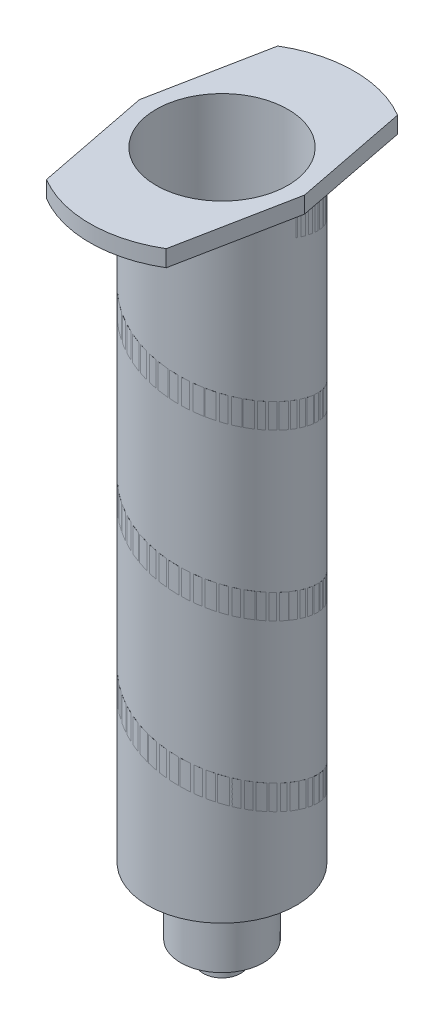
SolidWorks part; units mm, degrees
material "ABS PC"
ref_plane "Front Plane" through (0, 0, 0) normal (0, 0, 1) x (1, 0, 0)
ref_plane "Top Plane" through (0, 0, 0) normal (0, 1, 0) x (1, 0, 0)
ref_plane "Right Plane" through (0, 0, 0) normal (1, 0, 0) x (0, 0, -1)
sketch "Sketch2" plane through (0, 0, 0) normal (0, 1, 0) x (1, 0, 0)
  circle A0 centre (0, 0) radius 8.98
  circle A1 centre (0, 0) radius 7.98
  dimension "D1" = 17.96
  dimension "D2" = 1
extrude "Boss-Extrude1" add sketch "Sketch2" along normal blind 73
sketch "Sketch3" plane through (0, 73, 0) normal (0, 1, 0) x (1, 0, 0)
  line L0 (-10, 0) -> (10, 0) construction
  line L1 (10, -16) -> (-10, -16) construction
  line L2 (10, -16) -> (10, 16) construction
  line L3 (10, 16) -> (-10, 16) construction
  line L4 (-10, -16) -> (-10, 16) construction
  line L5 (10, -16) -> (-10, 16) construction
  line L6 (10, 16) -> (-10, -16) construction
  line L7 (7.25, -14) -> (-7.25, -14) construction
  line L8 (7.25, -14) -> (7.25, 14) construction
  line L9 (7.25, 14) -> (-7.25, 14) construction
  line L10 (-7.25, -14) -> (-7.25, 14) construction
  line L11 (7.25, -14) -> (-7.25, 14) construction
  line L12 (7.25, 14) -> (-7.25, -14) construction
  line L13 (-10, 0) -> (-7.25, -14)
  line L14 (7.25, -14) -> (10, 0)
  line L15 (10, 0) -> (7.25, 14)
  line L16 (-7.25, 14) -> (-10, 0)
  circle A0 centre (0, 0) radius 8.98
  arc A1 (-7.25, 14) -> (7.25, 14) centre (0, 1.8594) cw
  arc A2 (-7.25, -14) -> (7.25, -14) centre (0, -1.8594) ccw
  circle M1 centre (0, 0) radius 8.98
  circle M2 centre (0, 0) radius 7.98
  dimension "D1" = 32
  dimension "D2" = 20
  dimension "D3" = 14.5
  dimension "D4" = 28
extrude "Boss-Extrude2" add sketch "Sketch3" along normal blind 2 contours M1 M2 | M2 | L13 A2 L14 L15 A1 L16 M1 region at (-8.2547, 73, -6.9273) region at (-8.726, 73, 0) region at (0, 73, 0)
sketch "Sketch4" plane through (0, 0, 0) normal (1, 0, 0) x (0, 0, -1)
  line L0 (-8.98, 0) -> (8.98, 0)
  line L1 (8.98, 0) -> (8.98, 8.9522) construction
  line L2 (8.98, 0) -> (8.98, 73) construction
  line L3 (8.98, 8.9522) -> (-8.98, 8.9522) construction
  line L4 (-8.98, 73) -> (-8.98, 0) construction
  line L5 (-8.98, 8.9522) -> (-8.98, 0) construction
  line L6 (8.98, 0) -> (8.98, -1) construction
  line L7 (8.98, 0) -> (5, -1)
  line L8 (5, -2.9015) -> (-5, -2.9015) construction
  line L9 (5, -2.9015) -> (5, 2.9015) construction
  line L10 (5, 2.9015) -> (-5, 2.9015) construction
  line L11 (-5, -2.9015) -> (-5, 2.9015) construction
  line L12 (5, -2.9015) -> (-5, 2.9015) construction
  line L13 (5, 2.9015) -> (-5, -2.9015) construction
  line L14 (5, -1) -> (5, 0)
  line L15 (5, 0) -> (8.98, 0)
  line L16 (0, 0) -> (0, -7.0679) construction
  point P10 (0, 0)
  dimension "D1" = 1
  dimension "D2" = 10
revolve "Revolve1" add sketch "Sketch4" angle 360 about L16 region at (0, -0.3333, -6.3267)
ref_plane "Plane1" through (0, -1, 0) normal (0, -1, 0) x (-1, 0, 0)
sketch "Sketch6" plane through (0, -1, 0) normal (0, -1, 0) x (-1, 0, 0)
  circle A0 centre (0, 0) radius 5
  circle A1 centre (0, 0) radius 2.25
  dimension "D1" = 4.5
extrude "Boss-Extrude3" add sketch "Sketch6" along normal blind 0.5 separate body
sketch "Sketch7" plane through (0, -1, 0) normal (0, -1, 0) x (-1, 0, 0)
  circle A0 centre (0, 0) radius 5
  circle A1 centre (0, 0) radius 4
  dimension "D1" = 1
extrude "Boss-Extrude4" add sketch "Sketch7" along normal blind 7
sketch "Sketch8" plane through (0, -1, 0) normal (0, -1, 0) x (-1, 0, 0)
  circle A0 centre (0, 0) radius 2.25
  circle A1 centre (0, 0) radius 1.25
  dimension "D1" = 2.5
extrude "Boss-Extrude5" add sketch "Sketch8" along normal blind 9.5
sketch "Sketch9" plane through (0, 73, 0) normal (0, -1, 0) x (1, 0, 0)
  circle A1 centre (0, 0) radius 7.98
extrude "Cut-Extrude2" cut sketch "Sketch9" against normal blind 9.5 contours A1
sketch "Sketch10" plane through (0, 0, 0) normal (0, 0, 1) x (1, 0, 0)
  line L0 (8.98, 0) -> (-8.98, 0) construction
  line L1 (-8.98, 0) -> (-8.855, 0)
  line L2 (-8.98, 0) -> (-8.98, 3)
  line L3 (-8.98, 3) -> (-8.855, 3)
  line L4 (-8.855, 0) -> (-8.855, 3)
  point P6 (0, 0)
  dimension "D1" = 3
  dimension "D2" = 0.125
ref_axis "Axis1" through (0, 73, 0) along (0, -1, 0)
sketch "Sketch12" plane through (0, 73, 0) normal (0, -1, 0) x (1, 0, 0)
  circle A0 centre (0, 0) radius 8.98
sketch "Sketch13" plane through (0, 73, 0) normal (0, -1, 0) x (1, 0, 0)
  circle A0 centre (0, 0) radius 8.98
ref_plane "Plane2" through (0, 71.5, 0) normal (0, -1, 0) x (-1, 0, 0)
sketch "Sketch15" plane through (0, 71.5, 0) normal (0, -1, 0) x (-1, 0, 0)
  circle A0 centre (0, 0) radius 8.98
curve "Helix/Spiral1" pitch 20 height 70 radius 8.98 left hand yes centre (0, 71.5, 0) axis (0, -1, 0) start towards (1, 0, 0)
sweep "Sweep1" add profiles "Sketch10" path "Helix/Spiral1"
